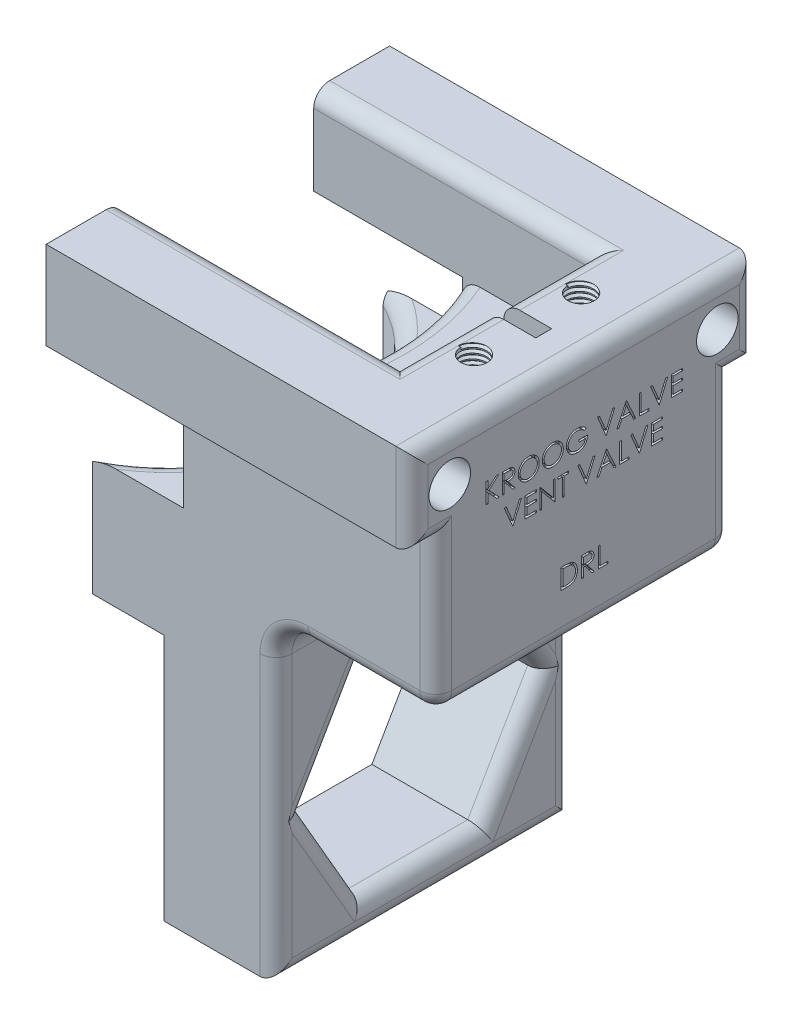
SolidWorks part; units mm, degrees
material "ABS"
ref_plane "Front Plane" through (0, 0, 0) normal (0, 0, 1) x (1, 0, 0)
ref_plane "Top Plane" through (0, 0, 0) normal (0, 1, 0) x (1, 0, 0)
ref_plane "Right Plane" through (0, 0, 0) normal (1, 0, 0) x (0, 0, -1)
sketch "Sketch2" plane through (0, 0, 0) normal (1, 0, 0) x (0, 0, -1)
  line L1 (9.5321, 16.51) -> (-9.5321, 16.51)
  line L2 (-9.5321, 16.51) -> (-19.0641, 0)
  line L3 (-19.0641, 0) -> (-9.5321, -16.51)
  line L4 (-9.5321, -16.51) -> (9.5321, -16.51)
  line L5 (9.5321, -16.51) -> (19.0641, 0)
  line L6 (19.0641, 0) -> (9.5321, 16.51)
  line L7 (-23.495, -21.59) -> (23.495, -21.59)
  line L8 (-23.495, -21.59) -> (-23.495, 52.07)
  line L9 (-23.495, 66.04) -> (23.495, 66.04)
  line L10 (23.495, -21.59) -> (23.495, 52.07)
  line L11 (-23.495, 66.04) -> (-27.305, 66.04)
  line L13 (-23.495, 52.07) -> (-27.305, 52.07)
  line L14 (-27.305, 66.04) -> (-27.305, 52.07)
  line L15 (23.495, 66.04) -> (27.305, 66.04)
  line L17 (23.495, 52.07) -> (27.305, 52.07)
  line L18 (27.305, 66.04) -> (27.305, 52.07)
  circle A0 centre (0, 0) radius 16.51 construction
  point P13 (0, -21.59)
  point P23 (0, 16.51)
  dimension "D1" = 33.02
  dimension "D2" = 5.08
  dimension "D3" = 46.99
  dimension "D4" = 87.63
  dimension "D5" = 13.97
  dimension "D6" = 3.81
extrude "Boss-Extrude1" add sketch "Sketch2" along normal blind 17.78
sketch "Sketch4" plane through (0, 0, 0) normal (-1, 0, 0) x (0, 0, 1)
  line L0 (-23.495, -21.59) -> (-23.495, 52.07) construction
  line L1 (-23.495, 17.78) -> (23.495, 17.78)
  line L2 (-23.495, 17.78) -> (-23.495, 52.07)
  line L4 (23.495, 17.78) -> (23.495, 52.07)
  line L5 (27.305, 66.04) -> (27.305, 52.07) construction
  line L6 (27.305, 52.07) -> (23.495, 52.07) construction
  line L7 (-23.495, 52.07) -> (-27.305, 52.07) construction
  line L8 (-27.305, 52.07) -> (-27.305, 66.04) construction
  line L9 (-27.305, 66.04) -> (27.305, 66.04) construction
  line L10 (27.305, 66.04) -> (27.305, 52.07)
  line L11 (27.305, 52.07) -> (23.495, 52.07)
  line L12 (-23.495, 52.07) -> (-27.305, 52.07)
  line L13 (-27.305, 52.07) -> (-27.305, 66.04)
  line L14 (-27.305, 66.04) -> (27.305, 66.04)
  line L15 (23.495, 52.07) -> (23.495, -21.59) construction
  dimension "D1" = 1.27
extrude "Boss-Extrude2" add sketch "Sketch4" along normal blind 11.43
sketch "Sketch5" plane through (0, 66.04, 0) normal (0, 1, 0) x (1, 0, 0)
  line L0 (0, 0) -> (-22.7305, 0) construction
  line L2 (-11.43, -27.305) -> (-11.43, 27.305) construction
  circle A0 centre (-22.7305, 0) radius 34.925
  circle A1 centre (-22.7305, 0) radius 25.4
  dimension "D2" = 69.85
  dimension "D3" = 50.8
  dimension "D1" = 11.3005
extrude "Cut-Extrude1" cut sketch "Sketch5" against normal blind 15.24 from offset 13.97 contours A1 A0 | A1 region at (-56.6676, 66.04, 0) region at (-22.7305, 66.04, 0) offset against normal yes
extrude "Cut-Extrude2" cut sketch "Sketch5<3>" against normal blind 38.1 from surface contours A1 region at (-22.7305, 66.04, 0) starting at face at (-1.8888, 36.83, 0)
sketch "Sketch5<3>" plane through (0, 66.04, 0) normal (0, 1, 0) x (1, 0, 0) same geometry as "Sketch5"
sketch "Sketch6" plane through (-11.43, 0, 0) normal (-1, 0, 0) x (0, 0, 1)
  line L4 (-27.305, 52.07) -> (27.305, 52.07)
  line L19 (-27.305, 52.07) -> (27.305, 52.07)
  line L23 (-27.305, 66.04) -> (-27.305, 52.07)
  line L25 (-27.305, 66.04) -> (-27.305, 52.07)
  line L27 (27.305, 52.07) -> (27.305, 66.04)
  line L28 (27.305, 52.07) -> (27.305, 66.04)
  line L29 (27.305, 66.04) -> (-27.305, 66.04)
  line L30 (27.305, 66.04) -> (-27.305, 66.04)
  dimension "D1" = 0
extrude "Boss-Extrude3" add sketch "Sketch6" along normal blind 3.5301
sketch "Sketch11" plane through (17.78, 0, 0) normal (1, 0, 0) x (0, 0, -1)
  line L0 (23.495, -21.59) -> (23.495, 52.07) construction
  line L2 (-23.495, 52.07) -> (-23.495, 27.94)
  line L3 (-23.495, 27.94) -> (23.495, 27.94)
  line L4 (23.495, 52.07) -> (23.495, 27.94)
  line L5 (-23.495, 52.07) -> (-23.495, -21.59) construction
  line L6 (23.495, 52.07) -> (27.305, 52.07) construction
  line L7 (27.305, 52.07) -> (27.305, 66.04) construction
  line L8 (-27.305, 52.07) -> (-23.495, 52.07) construction
  line L9 (-27.305, 66.04) -> (-27.305, 52.07) construction
  line L10 (27.305, 66.04) -> (-27.305, 66.04) construction
  line L11 (23.495, 52.07) -> (27.305, 52.07)
  line L12 (27.305, 52.07) -> (27.305, 66.04)
  line L13 (-27.305, 52.07) -> (-23.495, 52.07)
  line L14 (-27.305, 66.04) -> (-27.305, 52.07)
  line L15 (27.305, 66.04) -> (-27.305, 66.04)
  dimension "D1" = 38.1
extrude "Boss-Extrude4" add sketch "Sketch11" along normal blind 25.4
sketch "Sketch7" plane through (0, 66.04, 0) normal (0, 1, 0) x (1, 0, 0)
  line L1 (-14.9601, 15.24) -> (29.2359, 15.24)
  line L2 (-14.9601, 15.24) -> (-14.9601, -15.24)
  line L3 (-14.9601, -15.24) -> (29.2359, -15.24)
  line L4 (29.2359, 15.24) -> (29.2359, -15.24)
  line L5 (-14.9601, -27.305) -> (-14.9601, 27.305) construction
  point P6 (29.2359, 0)
  dimension "D1" = 30.48
  dimension "D2" = 44.196
extrude "Cut-Extrude3" cut sketch "Sketch7" against normal up to surface (13.97 mm away) up to face at (19.7631, 52.07, 0)
sketch "Sketch8" plane through (0, 66.04, 0) normal (0, 1, 0) x (1, 0, 0)
  line L0 (29.2359, -15.24) -> (29.2359, 15.24) construction
  line L1 (29.2359, -1.27) -> (36.8559, -1.27)
  line L2 (29.2359, -1.27) -> (29.2359, 1.27)
  line L3 (29.2359, 1.27) -> (36.8559, 1.27)
  line L4 (36.8559, -1.27) -> (36.8559, 1.27)
  point P6 (33.0459, -1.27)
  point P7 (29.2359, 0)
  dimension "D1" = 2.54
  dimension "D2" = 7.62
extrude "Cut-Extrude4" cut sketch "Sketch8" against normal blind 2.54
sketch "Sketch9" plane through (0, 66.04, 0) normal (0, 1, 0) x (1, 0, 0)
  line L0 (17.78, 23.495) -> (17.78, -23.495) construction
  line L1 (-14.9601, -23.495) -> (17.78, -23.495) construction
  line L2 (0, 0) -> (17.78, 0) construction
  line L4 (43.18, 27.305) -> (43.18, -27.305) construction
  circle A0 centre (34.29, -8.509) radius 1.27
  circle A1 centre (34.29, 8.509) radius 1.27
  point P0 (34.29, -8.509)
  point P9 (34.29, 8.509)
  dimension "D3" = 2.54
  dimension "D1" = 8.89
  dimension "D2" = 14.986
hole_wizard "Tap Drill for M5x0.8 Tap1" positions "Sketch9" profile "Sketch10" hole size "M5x0.8" standard "ANSI Metric"
sketch "Sketch10" plane through (34.29, 66.04, 8.509) normal (1, 0, 0) x (0, 0, 1)
  line L0 (0, 0) -> (0, 9.1358)
  line L1 (0, 9.1358) -> (2.1, 7.874)
  line L2 (2.1, 7.874) -> (2.1, 0)
  line L5 (2.1, 0) -> (0, 0)
  line L10 (0, 9.1358) -> (-2.1, 7.874) construction
  line L11 (0, -6.35) -> (0, 107.95) construction
  dimension "Hole Dia." = 4.2
  dimension "Hole Depth" = 7.874
  dimension "Drill Angle" = 118
fillet "Fillet3" radius 2.54 2 edges at (2.6695, 36.83, 0) (12.1945, 52.07, 0)
fillet "Fillet5" radius 5.08 1 edges at (17.78, 27.94, 0)
fillet "Fillet6" radius 2.54 21 edges at (33.02, 27.94, 23.495) (19.2679, 26.4521, 23.495) (33.02, 27.94, -23.495) (19.2679, 26.4521, -23.495) (17.78, -21.59, 0) (17.78, 0.635, 23.495) (17.78, 0.635, -23.495) (17.78, 16.51, 0) (17.78, 8.255, 14.2981) (17.78, -8.255, 14.2981) (17.78, -16.51, 0) (17.78, -8.255, -14.2981) (17.78, 8.255, -14.2981) (43.18, 40.005, -23.495) (43.18, 27.94, 0) (43.18, 40.005, 23.495) (43.18, 52.07, 25.4) (43.18, 59.055, 27.305) (43.18, 66.04, 0) (43.18, 59.055, -27.305) (43.18, 52.07, -25.4)
fillet "Fillet7" radius 2.54 4 edges at (29.2359, 66.04, 8.255) (7.1379, 66.04, 15.24) (29.2359, 66.04, -8.255) (7.1379, 66.04, -15.24)
sketch "Sketch15" plane through (-14.9601, 0, 0) normal (-1, 0, 0) x (0, 0, 1)
  line L0 (-27.305, 59.055) -> (-15.24, 59.055) construction
  line L1 (-27.305, 66.04) -> (-27.305, 52.07) construction
  line L2 (-15.24, 52.07) -> (-15.24, 63.5) construction
  line L3 (-21.2725, 52.07) -> (-21.2725, 66.04) construction
  line L4 (-27.305, 52.07) -> (-15.24, 52.07) construction
  line L5 (-17.78, 66.04) -> (-27.305, 66.04) construction
  line L6 (0, 0) -> (0, 66.04) construction
  line L7 (1.27, 66.04) -> (-1.27, 66.04) construction
  circle A0 centre (-21.2725, 59.055) radius 3.302
  circle A1 centre (21.2725, 59.055) radius 3.302
  dimension "D1" = 6.604
extrude "Cut-Extrude7" cut sketch "Sketch15" against normal through all
sketch "Sketch16" plane through (43.18, 0, 0) normal (1, 0, 0) x (0, 0, -1)
  line L0 (-20.955, 53.34) -> (20.955, 53.34) construction
  line L1 (-20.955, 48.26) -> (20.955, 48.26) construction
  line L2 (-20.955, 54.61) -> (-20.955, 30.48) construction
  line L3 (20.955, 30.48) -> (20.955, 54.61) construction
  line L4 (-20.955, 35.56) -> (20.955, 35.56) construction
  line L5 (-20.955, 30.48) -> (20.955, 30.48) construction
  text T0 "KROOG VALVE"
  text T1 "VENT VALVE"
  text T2 "DRL"
  dimension "D1" = 5.08
  dimension "D2" = 12.7
  dimension "D3" = 5.08
extrude "Cut-Extrude8" cut sketch "Sketch16" against normal blind 0.635
thread "Thread1" pitch 0.8 method cut profile "Thread Profile1" start angle 0, offset 0.254, length 10, pitch 0.8, diameter 4.2
ref_plane "Plane1" through (32.19, 66.294, 8.509) normal (0, 0, 1) x (-1, 0, 0)
sketch "Thread Profile1" plane through (32.19, 66.294, 8.509) normal (0, 0, 1) x (-1, 0, 0)
  line L0 (0, 0) -> (0, 0.8) construction
  line L1 (0, 0) -> (0.433, 0.25)
  line L2 (0.433, 0.25) -> (0.433, 0.35)
  line L3 (0.433, 0.35) -> (0, 0.6)
  line L4 (0.433, 0.3) -> (0, 0.3) construction
  line L11 (0, 0) -> (0, 0.6)
  point P2 (0, 0)
  dimension "Pitch" = 0.8
  dimension "Profile_Angle" = 60
  dimension "Profile_Land" = 0.1
  dimension "Profile_Height" = 0.433
thread "Thread2" pitch 0.8 method cut profile "Thread Profile2" start angle 0, offset 0.254, length 10, pitch 0.8, diameter 4.2
ref_plane "Plane2" through (32.19, 66.294, -8.509) normal (0, 0, 1) x (-1, 0, 0)
sketch "Thread Profile2" plane through (32.19, 66.294, -8.509) normal (0, 0, 1) x (-1, 0, 0)
  line L0 (0, 0) -> (0, 0.8) construction
  line L1 (0, 0) -> (0.433, 0.25)
  line L2 (0.433, 0.25) -> (0.433, 0.35)
  line L3 (0.433, 0.35) -> (0, 0.6)
  line L4 (0.433, 0.3) -> (0, 0.3) construction
  line L11 (0, 0) -> (0, 0.6)
  point P2 (0, 0)
  dimension "Pitch" = 0.8
  dimension "Profile_Angle" = 60
  dimension "Profile_Land" = 0.1
  dimension "Profile_Height" = 0.433
